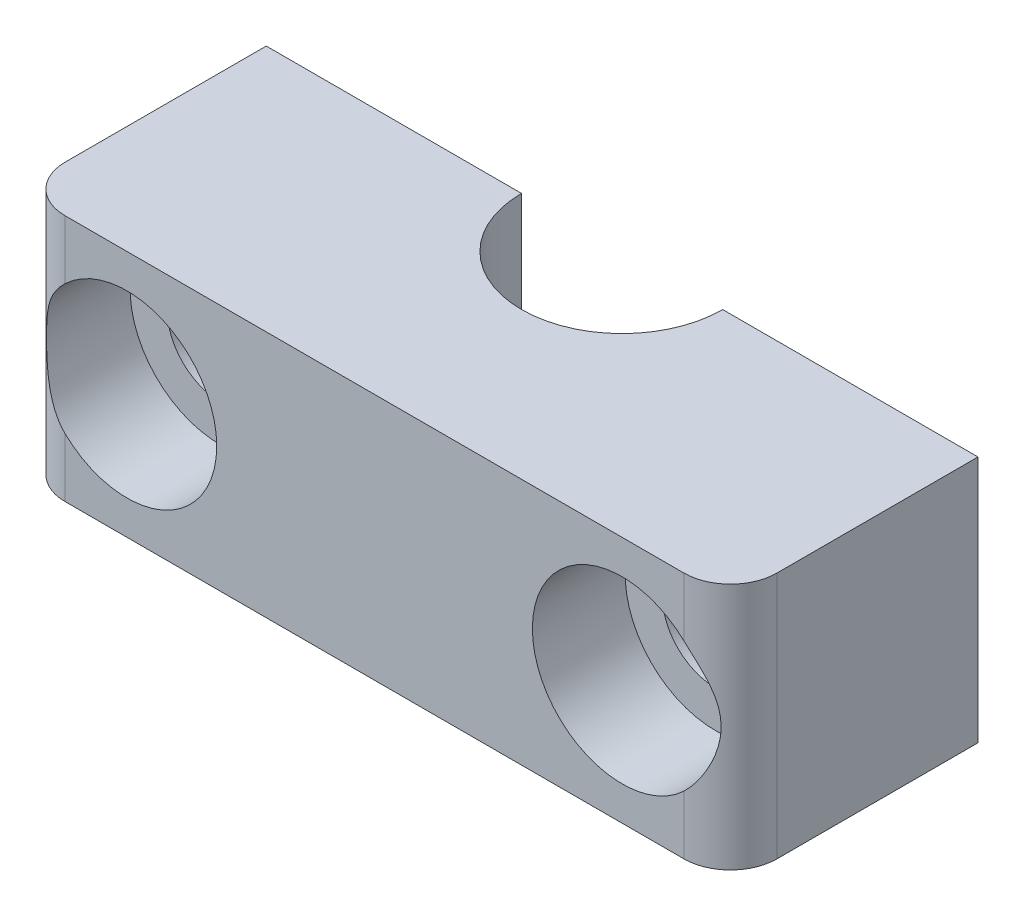
SolidWorks part; units mm, degrees
ref_plane "Front Plane" through (0, 0, 0) normal (0, 0, 1) x (1, 0, 0)
ref_plane "Top Plane" through (0, 0, 0) normal (0, 1, 0) x (1, 0, 0)
ref_plane "Right Plane" through (0, 0, 0) normal (1, 0, 0) x (0, 0, -1)
sketch "Sketch1" plane through (0, 0, 0) normal (0, 0, 1) x (1, 0, 0)
  line L1 (-11.5, 4) -> (11.5, 4)
  line L2 (-11.5, 4) -> (-11.5, -4)
  line L3 (-11.5, -4) -> (11.5, -4)
  line L4 (11.5, 4) -> (11.5, -4)
  line L5 (-11.5, 4) -> (11.5, -4) construction
  line L6 (-11.5, -4) -> (11.5, 4) construction
  point P0 (0, 0)
  dimension "D1" = 23
  dimension "D2" = 8
extrude "Boss-Extrude1" add sketch "Sketch1" along normal blind 8
sketch "Sketch2" plane through (0, 0, 0) normal (0, 1, 0) x (1, 0, 0)
  circle A0 centre (0, 0) radius 5
  point P2 (0, 0)
  dimension "D1" = 10
extrude "Cut-Extrude1" cut sketch "Sketch2" against normal through all
hole_wizard "CBORE for M3 SHCS1" positions "Sketch4" profile "Sketch5" counterbore size "M3" standard "ANSI Metric" end condition through all
sketch "Sketch4" plane through (0, 0, 8) normal (0, 0, 1) x (1, 0, 0)
  line L0 (0, 0) -> (-11.5, 0) construction
  line L1 (-11.5, 4) -> (-11.5, -4) construction
  line L3 (0, 0) -> (0, 4) construction
  line L4 (11.5, 4) -> (-11.5, 4) construction
  point P0 (-8, 0)
  point P17 (-8.2621, 0)
  point P18 (0, 0)
  point P20 (0, 0)
  point P21 (8, 0)
  dimension "D1" = 16
sketch "Sketch5" plane through (-8, 0, 8) normal (1, 0, 0) x (0, -1, 0)
  line L0 (0, 0) -> (0, 8)
  line L1 (0, 8) -> (1.7, 8)
  line L3 (1.7, 8) -> (1.7, 3)
  line L4 (1.7, 3) -> (2.9, 3)
  line L5 (2.9, 3) -> (2.9, 0)
  line L7 (2.9, 0) -> (0, 0)
  line L11 (0, -6.35) -> (0, 107.95) construction
  dimension "Thru Hole Dia." = 3.4
  dimension "Thru Hole Depth" = 8
  dimension "C'Bore Dia." = 5.8
  dimension "C'Bore Depth" = 3
sketch "Sketch8" plane through (0, 0, 0) normal (0, 1, 0) x (1, 0, 0)
  circle A0 centre (0, 0) radius 3.25
  dimension "D1" = 6.5
extrude "Cut-Extrude2" cut sketch "Sketch8" along normal through all
fillet "Fillet1" radius 1.5 2 edges at (-11.5, 0, 8) (11.5, 0, 8)
